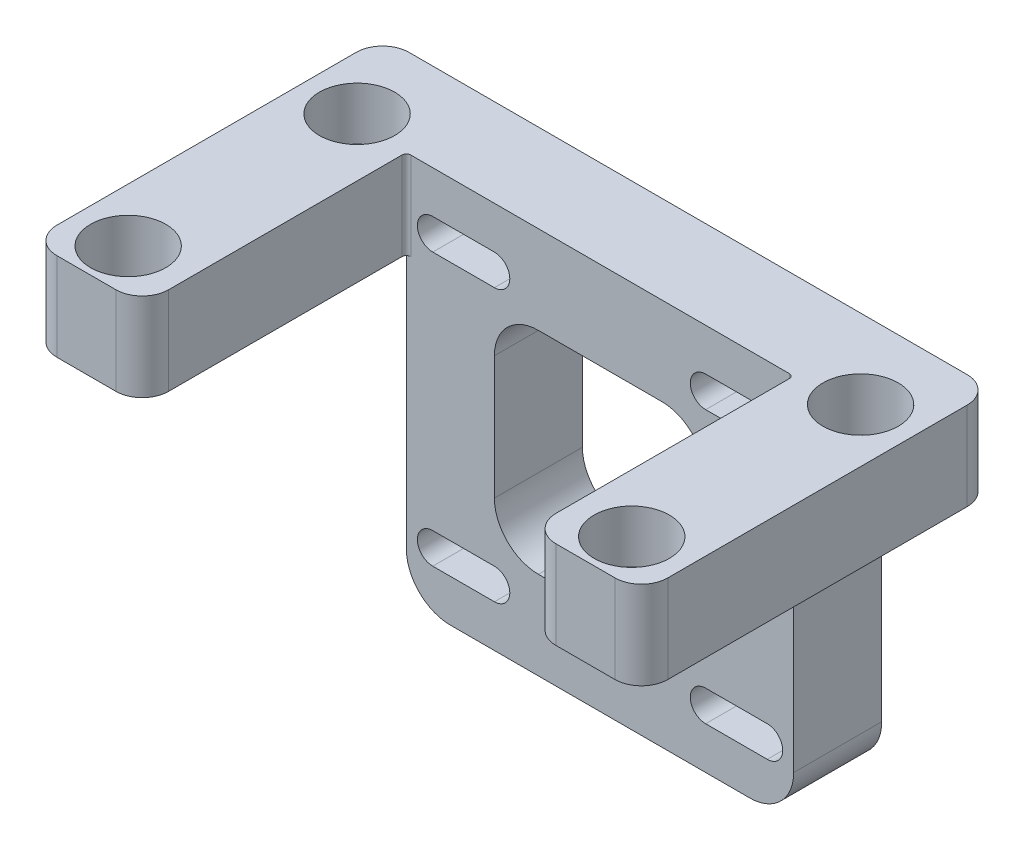
SolidWorks part; units mm, degrees
ref_plane "Front Plane" through (0, 0, 0) normal (0, 0, 1) x (1, 0, 0)
ref_plane "Top Plane" through (0, 0, 0) normal (0, 1, 0) x (1, 0, 0)
ref_plane "Right Plane" through (0, 0, 0) normal (1, 0, 0) x (0, 0, -1)
sketch "Sketch1" plane through (0, 0, 0) normal (0, 0, 1) x (1, 0, 0)
  line L0 (-19, 15.45) -> (-10.25, 15.45) construction
  line L1 (-22, 22) -> (22, 22)
  line L2 (-22, 22) -> (-22, -22)
  line L3 (-22, -22) -> (22, -22)
  line L4 (22, 22) -> (22, -22)
  line L5 (-22, 22) -> (22, -22) construction
  line L6 (-22, -22) -> (22, 22) construction
  line L7 (7, 12) -> (-7, 12)
  line L8 (12, 7) -> (12, -7)
  line L9 (7, -12) -> (-7, -12)
  line L10 (-12, 7) -> (-12, -7)
  line L11 (12, 12) -> (-12, -12) construction
  line L12 (12, -12) -> (-12, 12) construction
  line L13 (-19, 17.2) -> (-12, 17.2)
  line L14 (-19, 13.7) -> (-12, 13.7)
  line L15 (0, 0) -> (50000, 0) construction
  line L16 (-19, -17.2) -> (-12, -17.2)
  line L19 (12, 17.2) -> (19, 17.2)
  line L20 (12, 13.7) -> (19, 13.7)
  line L21 (10.25, 15.45) -> (19, 15.45) construction
  line L22 (-19, -13.7) -> (-12, -13.7)
  line L23 (12, -13.7) -> (19, -13.7)
  line L24 (12, -17.2) -> (19, -17.2)
  arc A0 (-12, -7) -> (-7, -12) centre (-7, -7) ccw
  arc A1 (7, -12) -> (12, -7) centre (7, -7) ccw
  arc A2 (12, 7) -> (7, 12) centre (7, 7) ccw
  arc A3 (-7, 12) -> (-12, 7) centre (-7, 7) ccw
  arc A4 (-19, 17.2) -> (-19, 13.7) centre (-19, 15.45) ccw
  arc A5 (19, 13.7) -> (19, 17.2) centre (19, 15.45) ccw
  circle A8 centre (0, 0) radius 12 construction
  arc A9 (12, 17.2) -> (12, 13.7) centre (12, 15.45) ccw
  arc A10 (-12, 17.2) -> (-12, 13.7) centre (-12, 15.45) cw
  arc A11 (-19, -17.2) -> (-19, -13.7) centre (-19, -15.45) cw
  arc A12 (-12, -17.2) -> (-12, -13.7) centre (-12, -15.45) ccw
  arc A13 (12, -17.2) -> (12, -13.7) centre (12, -15.45) cw
  arc A14 (19, -13.7) -> (19, -17.2) centre (19, -15.45) cw
  point P0 (0, 0)
  point P6 (0, 0)
  dimension "D4" = 5
  dimension "D9" = 1.75
  dimension "D1" = 44
  dimension "D2" = 44
  dimension "D3" = 24
  dimension "D5" = 38
  dimension "D6" = 1.75
  dimension "D7" = 15.45
  dimension "D8" = 7
extrude "Boss-Extrude1" add sketch "Sketch1" along normal blind 10
sketch "Sketch2" plane through (22, 0, 0) normal (1, 0, 0) x (0, 0, -1)
  line L0 (0, 12) -> (-40, 12)
  line L1 (0, -22) -> (0, 22) construction
  line L2 (0, 12) -> (0, 22)
  line L3 (0, 22) -> (-10, 22)
  line L4 (-40, 12) -> (-40, 16)
  line L5 (-40, 16) -> (0, 16) construction
  line L6 (-10, 22) -> (-40, 22)
  line L7 (-40, 22) -> (-40, 16)
  dimension "D1" = 4
  dimension "D2" = 40
  dimension "D3" = 12
extrude "Boss-Extrude2" add sketch "Sketch2" along normal blind 12.7
sketch "Sketch3" plane through (0, 12, 0) normal (0, -1, 0) x (1, 0, 0)
  line L0 (34.7, 0) -> (22, 0) construction
  line L1 (34.7, 40) -> (34.7, 0) construction
  line L2 (34.7, 40) -> (22, 40) construction
  circle A0 centre (28.6, 35) radius 2.6
  circle A1 centre (28.6, 9) radius 2.6
  dimension "D2" = 5.2
  dimension "D1" = 6.1
  dimension "D3" = 5
  dimension "D4" = 9
extrude "Cut-Extrude1" cut sketch "Sketch3" against normal through all
ref_plane "Plane1" through (0, 16, 0) normal (0, -1, 0) x (-1, 0, 0)
sketch "Sketch4" plane through (0, 16, 0) normal (0, -1, 0) x (-1, 0, 0)
  circle A0 centre (-28.6, -9) radius 4.275
  circle A1 centre (-28.6, -35) radius 4.275
  dimension "D1" = 8.55
  dimension "D2" = 8.55
extrude "Cut-Extrude2" cut sketch "Sketch4" against normal through all
ref_plane "Plane2" through (0, 0, 0) normal (1, 0, 0) x (0, 0, -1)
mirror "Mirror1" about plane through (0, 0, 0) normal (1, 0, 0) of "Cut-Extrude1", "Boss-Extrude2", "Cut-Extrude2"
fillet "Fillet1" radius 3 6 edges at (34.7, 17, 0) (-34.7, 17, 0) (34.7, 17, 40) (22, 17, 40) (-22, 17, 40) (-34.7, 17, 40)
fillet "Fillet2" radius 5 2 edges at (22, -22, 5) (-22, -22, 5)
fillet "Fillet3" radius 0.5 2 edges at (-22, 17, 10) (22, 17, 10)
